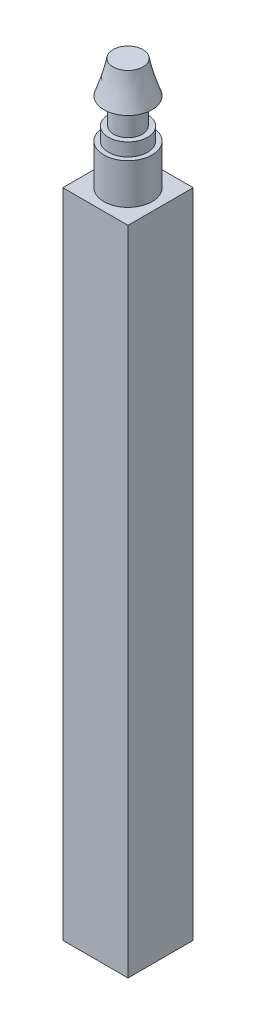
SolidWorks part; units mm, degrees
ref_plane "Front Plane" through (0, 0, 0) normal (0, 0, 1) x (1, 0, 0)
ref_plane "Top Plane" through (0, 0, 0) normal (0, 1, 0) x (1, 0, 0)
ref_plane "Right Plane" through (0, 0, 0) normal (1, 0, 0) x (0, 0, -1)
sketch "Sketch1" plane through (0, 0, 0) normal (0, 1, 0) x (1, 0, 0)
  circle A0 centre (0, 0) radius 1.85
  dimension "D1" = 3.7
extrude "Boss-Extrude1" add sketch "Sketch1" along normal blind 3.1
sketch "Sketch2" plane through (0, 3.1, 0) normal (0, 1, 0) x (1, 0, 0)
  circle A0 centre (0, 0) radius 1.5
  dimension "D1" = 3
extrude "Boss-Extrude2" add sketch "Sketch2" along normal blind 1
sketch "Sketch3" plane through (0, 4.1, 0) normal (0, 1, 0) x (1, 0, 0)
  circle A0 centre (0, 0) radius 1.1
  dimension "D1" = 2.2
extrude "Boss-Extrude3" add sketch "Sketch3" along normal blind 2
sketch "Sketch4" plane through (0, 6.1, 0) normal (0, 1, 0) x (1, 0, 0)
  circle A0 centre (0, 0) radius 1.85
  dimension "D1" = 3.7
ref_plane "Plane1" through (0, 8.6, 0) normal (0, 1, 0) x (1, 0, 0)
sketch "Sketch5" plane through (0, 8.6, 0) normal (0, 1, 0) x (1, 0, 0)
  circle A0 centre (0, 0) radius 1.15
  dimension "D1" = 2.3
loft "Loft1" add profiles "Sketch4", "Sketch5" connector at (0, 6.1, 1.85) connector at (0.6205, 8.6, 0.9683)
sketch "Sketch6" plane through (0, 0, 0) normal (0, -1, 0) x (1, 0, 0)
  line L1 (-2.5, 2.5) -> (2.5, 2.5)
  line L2 (-2.5, 2.5) -> (-2.5, -2.5)
  line L3 (-2.5, -2.5) -> (2.5, -2.5)
  line L4 (2.5, 2.5) -> (2.5, -2.5)
  line L5 (-2.5, 2.5) -> (2.5, -2.5) construction
  line L6 (-2.5, -2.5) -> (2.5, 2.5) construction
  point P0 (0, 0)
  dimension "D1" = 5
  dimension "D2" = 5
extrude "Boss-Extrude4" add sketch "Sketch6" along normal blind 50
sketch "Sketch7" plane through (0, -50, 0) normal (0, -1, 0) x (1, 0, 0)
  circle A0 centre (0, 0) radius 1
  dimension "D1" = 2
extrude "Cut-Extrude1" cut sketch "Sketch7" against normal blind 24
